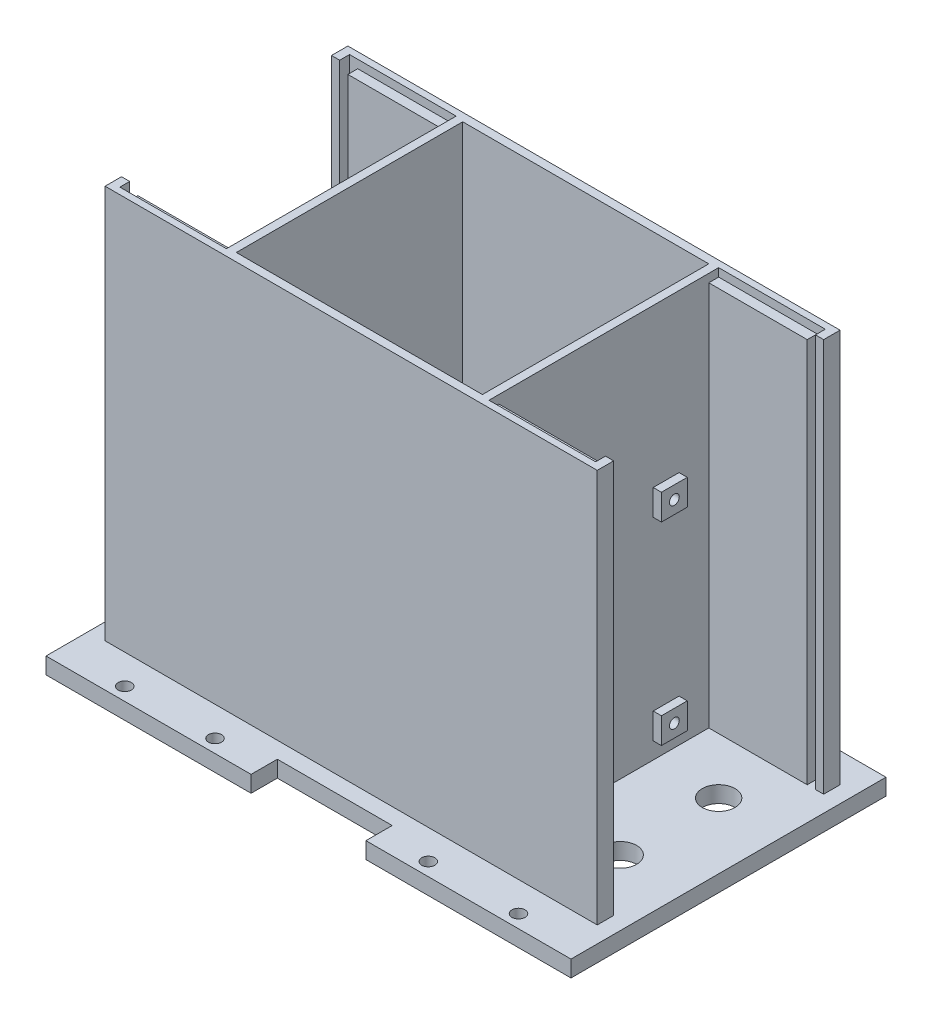
SolidWorks part; units mm, degrees
material "PPE"
ref_plane "Front Plane" through (0, 0, 0) normal (0, 0, 1) x (1, 0, 0)
ref_plane "Top Plane" through (0, 0, 0) normal (0, 1, 0) x (1, 0, 0)
ref_plane "Right Plane" through (0, 0, 0) normal (1, 0, 0) x (0, 0, -1)
sketch "Sketch1" plane through (0, 0, 0) normal (0, 1, 0) x (1, 0, 0)
  line L1 (-101.6, -101.6) -> (101.6, -101.6)
  line L2 (-101.6, -101.6) -> (-101.6, 101.6)
  line L3 (-101.6, 101.6) -> (101.6, 101.6)
  line L4 (101.6, -101.6) -> (101.6, 101.6)
  line L5 (-101.6, -101.6) -> (101.6, 101.6) construction
  line L6 (-101.6, 101.6) -> (101.6, -101.6) construction
  point P0 (0, 0)
  dimension "D1" = 203.2
  dimension "D2" = 203.2
extrude "Boss-Extrude1" add sketch "Sketch1" along normal blind 6.35
sketch "Sketch2" plane through (0, 6.35, 0) normal (0, 1, 0) x (1, 0, 0)
  line L0 (0, 0) -> (0, 106.1242) construction
  line L7 (-22.225, 101.6) -> (22.225, 101.6)
  line L8 (-22.225, 101.6) -> (-22.225, 55.88)
  line L9 (-22.225, 55.88) -> (22.225, 55.88)
  line L10 (22.225, 101.6) -> (22.225, 55.88)
  line L11 (-22.225, 101.6) -> (22.225, 55.88) construction
  line L12 (-22.225, 55.88) -> (22.225, 101.6) construction
  line L13 (101.6, 101.6) -> (-101.6, 101.6) construction
  line L14 (-101.6, -101.6) -> (101.6, -101.6) construction
  line L15 (-22.225, -101.6) -> (22.225, -101.6)
  line L16 (-22.225, -101.6) -> (-22.225, -50.8)
  line L17 (-22.225, -50.8) -> (22.225, -50.8)
  line L18 (22.225, -101.6) -> (22.225, -50.8)
  line L19 (-22.225, -101.6) -> (22.225, -50.8) construction
  line L20 (-22.225, -50.8) -> (22.225, -101.6) construction
  point P5 (0, 78.74)
  point P18 (0, -76.2)
  dimension "D3" = 44.45
  dimension "D4" = 45.72
  dimension "D5" = 44.45
  dimension "D6" = 50.8
extrude "Cut-Extrude1" cut sketch "Sketch2" against normal through all
sketch "Sketch3" plane through (0, 6.35, 0) normal (0, 1, 0) x (1, 0, 0)
  line L0 (-22.225, 101.6) -> (-101.6, 101.6) construction
  line L1 (-53.848, 88.9) -> (-28.448, 88.9)
  line L2 (-53.848, 88.9) -> (-53.848, 63.5)
  line L3 (-53.848, 63.5) -> (-28.448, 63.5)
  line L4 (-28.448, 88.9) -> (-28.448, 63.5)
  line L5 (-53.848, 88.9) -> (-28.448, 63.5) construction
  line L6 (-53.848, 63.5) -> (-28.448, 88.9) construction
  line L7 (-22.225, 101.6) -> (-22.225, 55.88) construction
  line L8 (-41.148, 76.2) -> (28.1634, 76.2) construction
  line L9 (-88.9, 63.5) -> (-63.5, 63.5)
  line L10 (-88.9, 63.5) -> (-88.9, 88.9)
  line L11 (-88.9, 88.9) -> (-63.5, 88.9)
  line L12 (-63.5, 63.5) -> (-63.5, 88.9)
  line L13 (-88.9, 63.5) -> (-63.5, 88.9) construction
  line L14 (-88.9, 88.9) -> (-63.5, 63.5) construction
  line L16 (-76.2, 96.52) -> (-16.3872, 96.52) construction
  circle A0 centre (-96.52, 76.2) radius 2.54
  circle A1 centre (-76.2, 96.52) radius 2.54
  circle A2 centre (-55.88, 76.2) radius 2.54 [skipped]
  circle A3 centre (-76.2, 55.88) radius 2.54
  circle A4 centre (-41.275, 96.52) radius 2.54
  circle A5 centre (-41.275, 55.88) radius 2.54
  point P0 (-41.148, 76.2)
  point P9 (-76.2, 76.2)
  point P27 (-76.2, 76.2)
  dimension "D8" = 5.08
  dimension "D11" = 5.08
  dimension "D1" = 25.4
  dimension "D2" = 25.4
  dimension "D3" = 12.7
  dimension "D4" = 6.223
  dimension "D5" = 25.4
  dimension "D6" = 25.4
  dimension "D7" = 9.652
  dimension "D9" = 7.62
  dimension "D12" = 34.925
  dimension "D10" = 4
extrude "Cut-Extrude2" cut sketch "Sketch3" against normal blind 6.35
mirror "Mirror1" about plane through (0, 0, 0) normal (1, 0, 0) of "Cut-Extrude2"
mirror "Mirror2" about plane through (0, 0, 0) normal (0, 0, 1) of "Mirror1"
sketch "Sketch4" plane through (0, 6.35, 0) normal (0, 1, 0) x (1, 0, 0)
  line L5 (101.6, -101.6) -> (101.6, 101.6) construction
  line L6 (-50.8, -44.45) -> (50.8, -44.45)
  line L8 (-50.8, -44.45) -> (-50.8, 49.53)
  line L9 (-50.8, 49.53) -> (50.8, 49.53)
  line L10 (50.8, -44.45) -> (50.8, 49.53)
  line L11 (-101.6, 101.6) -> (-101.6, -101.6) construction
  line L12 (-22.225, 55.88) -> (22.225, 55.88) construction
  line L13 (22.225, -50.8) -> (-22.225, -50.8) construction
  line L15 (-47.625, -41.275) -> (47.625, -41.275)
  line L16 (-47.625, -41.275) -> (-47.625, 46.355)
  line L17 (-47.625, 46.355) -> (47.625, 46.355)
  line L18 (47.625, -41.275) -> (47.625, 46.355)
  point P0 (0, 0)
  dimension "D1" = 50.8
  dimension "D2" = 50.8
  dimension "D3" = 6.35
  dimension "D4" = 6.35
  dimension "D5" = 3.175
  dimension "D6" = 3.175
  dimension "D7" = 3.175
  dimension "D8" = 3.175
extrude "Boss-Extrude2" add sketch "Sketch4" along normal blind 152.4
sketch "Sketch5" plane through (50.8, 0, 0) normal (1, 0, 0) x (0, 0, -1)
  line L5 (2.54, 158.75) -> (2.54, -3.612) construction
  line L6 (-44.45, 158.75) -> (49.53, 158.75) construction
  line L12 (-24.13, 107.95) -> (29.21, 107.95) construction
  line L13 (-44.45, 6.35) -> (49.53, 6.35) construction
  line L14 (29.21, 107.95) -> (29.21, 6.35) construction
  line L15 (-24.13, 107.95) -> (-24.13, 6.35) construction
  line L17 (-26.59, 88.98) -> (-16.59, 88.98)
  line L18 (-26.59, 88.98) -> (-26.59, 98.98)
  line L19 (-26.59, 98.98) -> (-16.59, 98.98)
  line L20 (-16.59, 88.98) -> (-16.59, 98.98)
  line L21 (-26.59, 88.98) -> (-16.59, 98.98) construction
  line L22 (-26.59, 98.98) -> (-16.59, 88.98) construction
  line L23 (21.67, 87.71) -> (31.67, 87.71)
  line L24 (21.67, 87.71) -> (21.67, 97.71)
  line L25 (21.67, 97.71) -> (31.67, 97.71)
  line L26 (31.67, 87.71) -> (31.67, 97.71)
  line L27 (21.67, 87.71) -> (31.67, 97.71) construction
  line L28 (21.67, 97.71) -> (31.67, 87.71) construction
  line L29 (-26.59, 6.43) -> (-16.59, 6.43)
  line L30 (-26.59, 6.43) -> (-26.59, 16.43)
  line L31 (-26.59, 16.43) -> (-16.59, 16.43)
  line L32 (-16.59, 6.43) -> (-16.59, 16.43)
  line L33 (-26.59, 6.43) -> (-16.59, 16.43) construction
  line L34 (-26.59, 16.43) -> (-16.59, 6.43) construction
  line L35 (21.67, 12.78) -> (31.67, 12.78)
  line L36 (21.67, 12.78) -> (21.67, 22.78)
  line L37 (21.67, 22.78) -> (31.67, 22.78)
  line L38 (31.67, 12.78) -> (31.67, 22.78)
  line L39 (21.67, 12.78) -> (31.67, 22.78) construction
  line L40 (21.67, 22.78) -> (31.67, 12.78) construction
  circle A0 centre (-21.59, 93.98) radius 1.6
  circle A1 centre (26.67, 92.71) radius 1.6
  circle A2 centre (26.67, 17.78) radius 1.6
  circle A3 centre (-21.59, 11.43) radius 1.6
  point P2 (2.54, 107.95)
  dimension "D3" = 3.2
  dimension "D6" = 3.2
  dimension "D9" = 3.2
  dimension "D12" = 3.2
  dimension "D1" = 53.34
  dimension "D2" = 101.6
  dimension "D4" = 2.54
  dimension "D5" = 13.97
  dimension "D7" = 2.54
  dimension "D8" = 15.24
  dimension "D10" = 2.54
  dimension "D11" = 90.17
  dimension "D13" = 2.54
  dimension "D14" = 96.52
  dimension "D15" = 10
  dimension "D16" = 10
  dimension "D17" = 10
  dimension "D18" = 10
  dimension "D19" = 10
  dimension "D20" = 10
  dimension "D21" = 10
  dimension "D22" = 10
extrude "Boss-Extrude3" add sketch "Sketch5" along normal blind 3.175
ref_plane "Plane1" through (53.975, 0, 0) normal (1, 0, 0) x (0, 0, -1)
sketch "Sketch8" plane through (53.975, 0, 0) normal (1, 0, 0) x (0, 0, -1)
  circle A0 centre (-21.59, 93.98) radius 1.905
  circle A1 centre (26.67, 92.71) radius 1.905
  circle A2 centre (-21.59, 11.43) radius 1.905
  circle A3 centre (26.67, 17.78) radius 1.905
  dimension "D1" = 3.81
  dimension "D2" = 3.81
  dimension "D3" = 3.81
  dimension "D4" = 3.81
extrude "Cut-Extrude3" cut sketch "Sketch8" against normal up to next
sketch "Sketch9" plane through (50.8, 0, 0) normal (1, 0, 0) x (0, 0, -1)
  line L0 (-44.45, 158.75) -> (49.53, 158.75) construction
  line L1 (-44.45, 6.35) -> (-38.1, 6.35)
  line L2 (-44.45, 6.35) -> (-44.45, 158.75)
  line L3 (-44.45, 158.75) -> (-38.1, 158.75)
  line L4 (-38.1, 6.35) -> (-38.1, 158.75)
  line L6 (49.53, 6.35) -> (43.18, 6.35)
  line L7 (49.53, 6.35) -> (49.53, 158.75)
  line L8 (49.53, 158.75) -> (43.18, 158.75)
  line L9 (43.18, 6.35) -> (43.18, 158.75)
  dimension "D1" = 6.35
  dimension "D2" = 6.35
extrude "Boss-Extrude4" add sketch "Sketch9" along normal blind 44.45
sketch "Sketch12" plane through (0, 158.75, 0) normal (0, 1, 0) x (1, 0, 0)
  line L0 (95.25, -38.1) -> (50.8, -38.1) construction
  line L1 (92.075, -38.1) -> (88.9, -38.1)
  line L2 (92.075, -38.1) -> (92.075, -41.91)
  line L3 (92.075, -41.91) -> (88.9, -41.91)
  line L4 (88.9, -38.1) -> (88.9, -41.91)
  line L5 (95.25, -38.1) -> (95.25, -44.45) construction
  dimension "D1" = 3.175
  dimension "D2" = 3.175
  dimension "D3" = 3.81
extrude "Cut-Extrude4" cut sketch "Sketch12" against normal up to surface (152.4 mm away) up to face at (-41.148, 6.35, 76.2)
ref_plane "Plane2" through (0, 0, -2.54) normal (0, 0, -1) x (-1, 0, 0)
sketch "Sketch13" plane through (0, 158.75, 0) normal (0, 1, 0) x (1, 0, 0)
  line L1 (88.9, -41.91) -> (50.8, -41.91)
  line L2 (88.9, -41.91) -> (88.9, -38.1)
  line L3 (88.9, -38.1) -> (50.8, -38.1)
  line L4 (50.8, -41.91) -> (50.8, -38.1)
  line L6 (88.9, -38.1) -> (88.9, -41.91) construction
  dimension "D1" = 3.81
extrude "Cut-Extrude5" cut sketch "Sketch13" against normal blind 3.175
mirror "Mirror3" about plane through (0, 0, -2.54) normal (0, 0, -1) of "Cut-Extrude5", "Cut-Extrude4"
sketch "Sketch14" plane through (-50.8, 0, 0) normal (-1, 0, 0) x (0, 0, 1)
  line L0 (-49.53, 158.75) -> (44.45, 158.75) construction
  line L1 (-49.53, 6.35) -> (-43.18, 6.35)
  line L2 (-49.53, 6.35) -> (-49.53, 158.75)
  line L3 (-49.53, 158.75) -> (-43.18, 158.75)
  line L4 (-43.18, 6.35) -> (-43.18, 158.75)
  line L6 (44.45, 6.35) -> (38.1, 6.35)
  line L7 (44.45, 6.35) -> (44.45, 158.75)
  line L8 (44.45, 158.75) -> (38.1, 158.75)
  line L9 (38.1, 6.35) -> (38.1, 158.75)
  dimension "D1" = 6.35
  dimension "D2" = 6.35
extrude "Boss-Extrude5" add sketch "Sketch14" along normal blind 44.45
sketch "Sketch15" plane through (0, 158.75, 0) normal (0, 1, 0) x (1, 0, 0)
  line L0 (-95.25, -38.1) -> (-50.8, -38.1) construction
  line L1 (-92.075, -38.1) -> (-88.9, -38.1)
  line L2 (-92.075, -38.1) -> (-92.075, -41.91)
  line L3 (-92.075, -41.91) -> (-88.9, -41.91)
  line L4 (-88.9, -38.1) -> (-88.9, -41.91)
  line L5 (-95.25, -44.45) -> (-95.25, -38.1) construction
  point P6 (-92.075, -40.005)
  dimension "D1" = 3.175
  dimension "D2" = 3.175
  dimension "D3" = 3.81
extrude "Cut-Extrude6" cut sketch "Sketch15" against normal blind 152.4
sketch "Sketch16" plane through (0, 158.75, 0) normal (0, 1, 0) x (1, 0, 0)
  line L0 (-95.25, -44.45) -> (95.25, -44.45) construction
  line L1 (-88.9, -38.1) -> (-50.8, -38.1)
  line L2 (-88.9, -38.1) -> (-88.9, -41.91)
  line L3 (-88.9, -41.91) -> (-50.8, -41.91)
  line L4 (-50.8, -38.1) -> (-50.8, -41.91)
  line L5 (-50.8, 43.18) -> (-50.8, -38.1) construction
  dimension "D1" = 2.54
extrude "Cut-Extrude7" cut sketch "Sketch16" against normal blind 3.175
mirror "Mirror4" about plane through (0, 0, -2.54) normal (0, 0, -1) of "Cut-Extrude6", "Cut-Extrude7"
sketch "Sketch17" plane through (0, 6.35, 0) normal (0, 1, 0) x (1, 0, 0)
  line L0 (-50.8, 2.54) -> (114.4914, 2.54) construction
  line L1 (-47.625, -41.275) -> (47.625, -41.275) construction
  line L3 (-50.8, 43.18) -> (-50.8, -38.1) construction
  line L7 (-88.9, 43.18) -> (-88.9, -38.1) construction
  line L9 (47.625, 46.355) -> (-47.625, 46.355) construction
  line L10 (-47.625, 46.355) -> (-47.625, -41.275) construction
  line L11 (47.625, -41.275) -> (47.625, 46.355) construction
  circle A0 centre (-76.2, -16.51) radius 6.35
  circle A1 centre (-76.2, 21.59) radius 6.35
  circle A2 centre (-28.575, 27.305) radius 6.35
  circle A3 centre (28.575, -22.225) radius 6.35
  dimension "D1" = 12.7
  dimension "D2" = 12.7
  dimension "D4" = 12.7
  dimension "D6" = 19.05
  dimension "D7" = 12.7
  dimension "D8" = 19.05
  dimension "D9" = 19.05
  dimension "D3" = 19.05
  dimension "D5" = 19.05
extrude "Cut-Extrude8" cut sketch "Sketch17" against normal up to next
mirror "Mirror5" about plane through (0, 0, 0) normal (1, 0, 0) of face at (-76.2, 0, 10.16) of face at (-76.2, 0, -27.94)
sketch "Sketch18" plane through (0, 6.35, 0) normal (0, 1, 0) x (1, 0, 0)
  line L0 (-22.225, 101.6) -> (-22.225, 55.88) construction
  line L1 (-101.6, 101.6) -> (-22.225, 101.6)
  line L2 (-101.6, 101.6) -> (-101.6, 60.96)
  line L3 (-101.6, 60.96) -> (-22.225, 60.96)
  line L4 (-22.225, 101.6) -> (-22.225, 60.96)
  line L5 (22.225, 55.88) -> (22.225, 101.6) construction
  line L6 (101.6, 101.6) -> (22.225, 101.6)
  line L7 (101.6, 101.6) -> (101.6, 60.96)
  line L8 (101.6, 60.96) -> (22.225, 60.96)
  line L9 (22.225, 101.6) -> (22.225, 60.96)
  line L10 (-22.225, -50.8) -> (-22.225, -101.6) construction
  line L11 (-101.6, -101.6) -> (-22.225, -101.6)
  line L12 (-101.6, -101.6) -> (-101.6, -60.96)
  line L13 (-101.6, -60.96) -> (-22.225, -60.96)
  line L14 (-22.225, -101.6) -> (-22.225, -60.96)
  line L15 (22.225, -101.6) -> (22.225, -50.8) construction
  line L16 (101.6, -101.6) -> (22.225, -101.6)
  line L17 (101.6, -101.6) -> (101.6, -60.96)
  line L18 (101.6, -60.96) -> (22.225, -60.96)
  line L19 (22.225, -101.6) -> (22.225, -60.96)
  dimension "D1" = 40.64
  dimension "D2" = 40.64
  dimension "D3" = 40.64
  dimension "D4" = 40.64
extrude "Cut-Extrude9" cut sketch "Sketch18" against normal through all
scale "Scale1" [suppressed]
